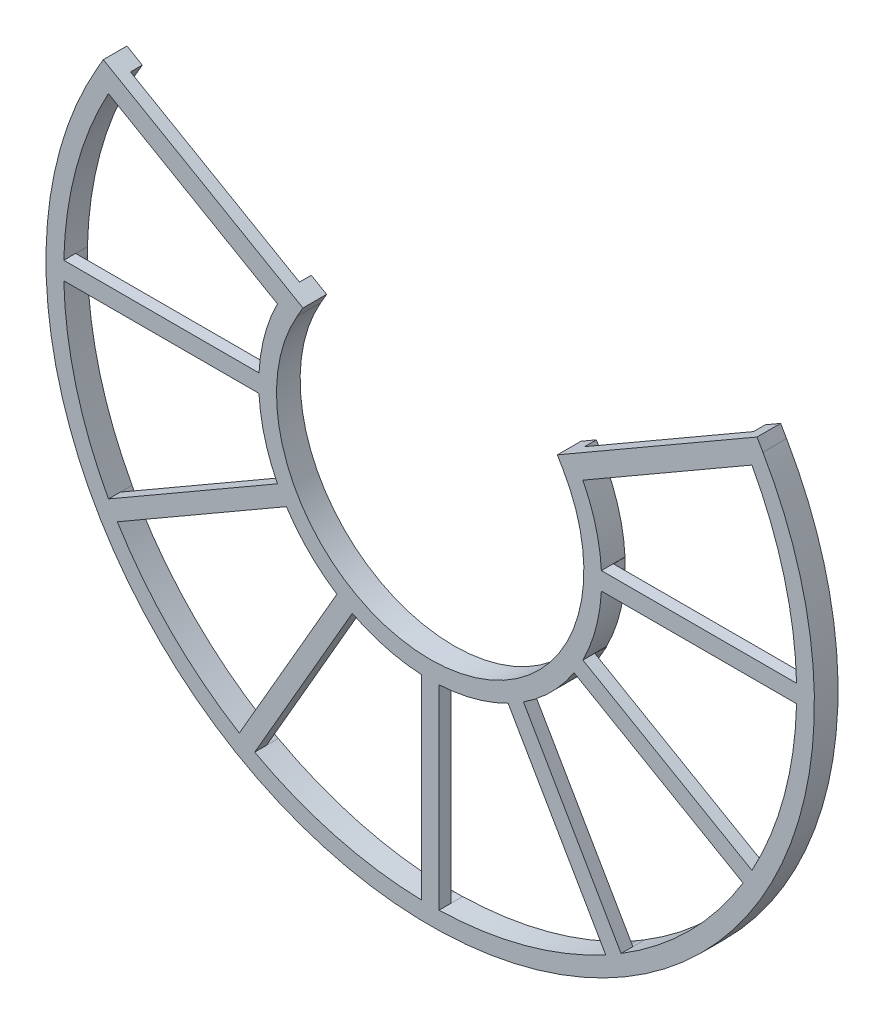
SolidWorks part; units mm, degrees
ref_plane "Plan de face" through (0, 0, 0) normal (0, 0, 1) x (1, 0, 0)
ref_plane "Plan de dessus" through (0, 0, 0) normal (0, 1, 0) x (1, 0, 0)
ref_plane "Plan de droite" through (0, 0, 0) normal (1, 0, 0) x (0, 0, -1)
sketch "Esquisse1" plane through (0, 0, 0) normal (0, 0, 1) x (1, 0, 0)
  line L0 (0, 0) -> (83.239, 0) construction
  line L1 (11.2583, 6.5) -> (28.1458, 16.25)
  line L2 (32.5, 0) -> (13, 0)
  line L3 (12.9156, 6.5908) -> (27.2139, 14.8459)
  line L4 (14.4806, 0.75) -> (30.9909, 0.75)
  arc A2 (13, 0) -> (11.2583, 6.5) centre (0, 0) ccw
  arc A3 (32.5, 0) -> (28.1458, 16.25) centre (0, 0) ccw
  arc A4 (12.9156, 6.5908) -> (14.4806, 0.75) centre (0, 0) cw
  arc A5 (27.2139, 14.8459) -> (30.9909, 0.75) centre (0, 0) cw
  point P8 (12.557, 3.3646)
  dimension "D1" = 13
  dimension "D2" = 32.5
  dimension "D5" = 1.5
  dimension "D6" = 1.5
  dimension "D3" = 0.75
  dimension "D4" = 0.75
extrude "Boss.-Extru.1" add sketch "Esquisse1" along normal blind 2
sketch "Esquisse2" plane through (0, 0, 0) normal (-0.5, 0.866, 0) x (0.866, 0.5, 0)
  line L0 (32.5, 0) -> (13, 0) construction
  line L1 (14.5, 0) -> (31, 0)
  line L2 (14.5, 0) -> (14.5, -1)
  line L3 (14.5, -1) -> (31, -1)
  line L4 (31, 0) -> (31, -1)
  line L5 (13, -2) -> (13, 0) construction
  line L6 (32.5, -2) -> (32.5, 0) construction
  line L7 (27.2139, -2) -> (30.9909, -2) construction
  dimension "D1" = 1.5
  dimension "D2" = 1.5
  dimension "D3" = 1
extrude "Enlèv. mat.-Extru.1" cut sketch "Esquisse2" against normal up to surface (0.75 mm away) up to face at (20.0647, 10.7184, 1)
sketch "Esquisse3" plane through (0, 0, 0) normal (0, -1, 0) x (1, 0, 0)
  line L0 (13, 0) -> (32.5, 0) construction
  line L1 (14.5, 0) -> (31, 0)
  line L2 (14.5, 0) -> (14.5, 1)
  line L3 (14.5, 1) -> (31, 1)
  line L4 (31, 0) -> (31, 1)
  line L5 (13, 2) -> (13, 0) construction
  line L6 (32.5, 2) -> (32.5, 0) construction
  line L7 (13, 2) -> (32.5, 2) construction
  dimension "D1" = 1.5
  dimension "D2" = 1.5
  dimension "D3" = 1
extrude "Enlèv. mat.-Extru.2" cut sketch "Esquisse3" against normal up to surface (0.75 mm away) up to face at (22.7358, 0.75, 1)
pattern_circular "Répétition circulaire1" count 8 every 29.999 about axis through (0, 0, 0) along (0, 0, -1) of "Boss.-Extru.1", "Enlèv. mat.-Extru.1", "Enlèv. mat.-Extru.2"
sketch "Esquisse5" plane through (0, 0, 0) normal (-0.5, 0.866, 0) x (0.866, 0.5, 0)
  line L8 (32.5, 0) -> (31, 0)
  line L9 (31, 0) -> (31, -1)
  line L10 (31, -1) -> (14.5, -1)
  line L11 (14.5, -1) -> (14.5, 0)
  line L12 (14.5, 0) -> (13, 0)
  line L13 (13, 0) -> (13, -2)
  line L14 (13, -2) -> (32.5, -2)
  line L15 (32.5, -2) -> (32.5, 0)
  line L16 (32.5, 0) -> (31, 0)
  line L17 (31, 0) -> (31, -1)
  line L18 (31, -1) -> (14.5, -1)
  line L19 (14.5, -1) -> (14.5, 0)
  line L20 (14.5, 0) -> (13, 0)
  line L21 (13, 0) -> (13, -2)
  line L22 (13, -2) -> (32.5, -2)
  line L23 (32.5, -2) -> (32.5, 0)
  dimension "D1" = 0
extrude "Boss.-Extru.2" add sketch "Esquisse5" along normal blind 1
sketch "Esquisse6" plane through (0, 0, 0) normal (0.4999, 0.8661, 0) x (0.8661, -0.4999, 0)
  line L8 (-14.5, -1) -> (-31, -1)
  line L9 (-31, -1) -> (-31, 0)
  line L10 (-31, 0) -> (-32.5, 0)
  line L11 (-32.5, 0) -> (-32.5, -2)
  line L12 (-32.5, -2) -> (-13, -2)
  line L13 (-13, -2) -> (-13, 0)
  line L14 (-13, 0) -> (-14.5, 0)
  line L15 (-14.5, 0) -> (-14.5, -1)
  line L16 (-14.5, -1) -> (-31, -1)
  line L17 (-31, -1) -> (-31, 0)
  line L18 (-31, 0) -> (-32.5, 0)
  line L19 (-32.5, 0) -> (-32.5, -2)
  line L20 (-32.5, -2) -> (-13, -2)
  line L21 (-13, -2) -> (-13, 0)
  line L22 (-13, 0) -> (-14.5, 0)
  line L23 (-14.5, 0) -> (-14.5, -1)
  dimension "D1" = 0
extrude "Boss.-Extru.3" add sketch "Esquisse6" along normal blind 1
